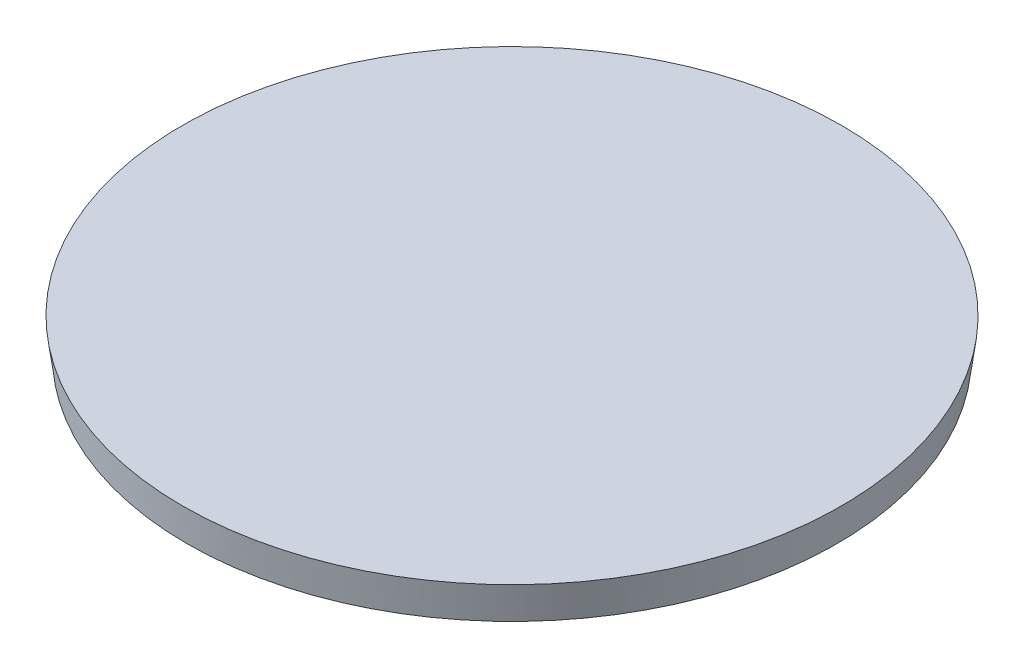
SolidWorks part; units mm, degrees
ref_plane "Front Plane" through (0, 0, 0) normal (0, 0, 1) x (1, 0, 0)
ref_plane "Top Plane" through (0, 0, 0) normal (0, 1, 0) x (1, 0, 0)
ref_plane "Right Plane" through (0, 0, 0) normal (1, 0, 0) x (0, 0, -1)
sketch "Sketch2" plane through (0, 0, 0) normal (0, 0, 1) x (1, 0, 0)
  line L0 (0, 0) -> (14.097, 0)
  line L1 (14.097, 0) -> (14.2976, 1.524)
  line L2 (14.2976, 1.524) -> (0, 1.524)
  line L4 (0, 1.524) -> (0, 0) construction
  line L5 (0, 1.524) -> (0, 0)
  dimension "D1" = 1.524
  dimension "D2" = 28.194
  dimension "D3" = 7.5
revolve "Revolve1" add sketch "Sketch2" angle 360 about L4
